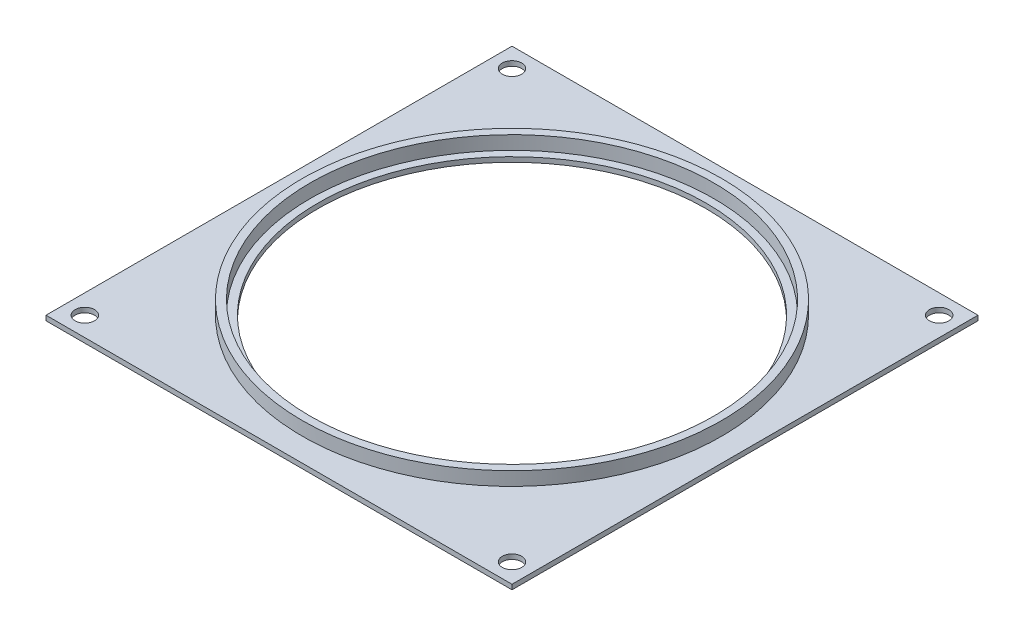
SolidWorks part; units mm, degrees
material "Alloy Steel"
ref_plane "Front Plane" through (0, 0, 0) normal (0, 0, 1) x (1, 0, 0)
ref_plane "Top Plane" through (0, 0, 0) normal (0, 1, 0) x (1, 0, 0)
ref_plane "Right Plane" through (0, 0, 0) normal (1, 0, 0) x (0, 0, -1)
sketch "Sketch1" plane through (0, 0, 0) normal (0, 1, 0) x (1, 0, 0)
  line L1 (-76.2, -76.2) -> (76.2, -76.2)
  line L2 (-76.2, -76.2) -> (-76.2, 76.2)
  line L3 (-76.2, 76.2) -> (76.2, 76.2)
  line L4 (76.2, -76.2) -> (76.2, 76.2)
  line L5 (-76.2, -76.2) -> (76.2, 76.2) construction
  line L6 (-76.2, 76.2) -> (76.2, -76.2) construction
  circle A0 centre (0, 0) radius 63.5
  circle A1 centre (-69.85, 69.85) radius 3.175
  circle A2 centre (69.85, 69.85) radius 3.175
  circle A3 centre (69.85, -69.85) radius 3.175
  circle A4 centre (-69.85, -69.85) radius 3.175
  point P18 (0, 0)
  dimension "D1" = 127
  dimension "D4" = 6.35
  dimension "D2" = 152.4
  dimension "D3" = 152.4
  dimension "D5" = 6.35
  dimension "D6" = 4
extrude "Boss-Extrude1" add sketch "Sketch1" along normal blind 1.5875
sketch "Sketch2" plane through (0, 1.5875, 0) normal (0, 1, 0) x (1, 0, 0)
  circle A0 centre (0, 0) radius 63.5 construction
  circle A1 centre (0, 0) radius 63.5
  circle A2 centre (0, 0) radius 66.04
  circle A3 centre (0, 0) radius 68.58
  dimension "D1" = 2.54
  dimension "D2" = 2.54
extrude "Boss-Extrude2" add sketch "Sketch2" along normal blind 4.445 contours A3 A2 region at (-66.6403, 1.5875, 0)
